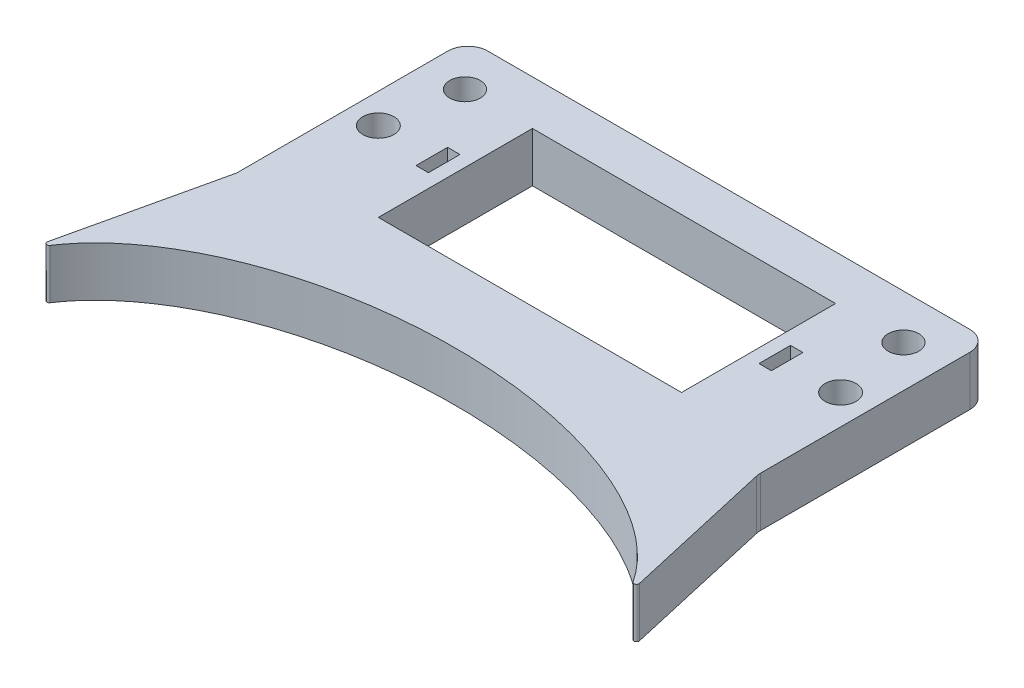
SolidWorks part; units mm, degrees
ref_plane "Front Plane" through (0, 0, 0) normal (0, 0, 1) x (1, 0, 0)
ref_plane "Top Plane" through (0, 0, 0) normal (0, 1, 0) x (1, 0, 0)
ref_plane "Right Plane" through (0, 0, 0) normal (1, 0, 0) x (0, 0, -1)
sketch "Sketch1" plane through (0, 0, 0) normal (0, 1, 0) x (1, 0, 0)
  line L1 (-52.5, -27.5) -> (52.5, -27.5)
  line L2 (-52.5, -27.5) -> (-52.5, 27.5)
  line L3 (-52.5, 27.5) -> (52.5, 27.5)
  line L4 (52.5, -27.5) -> (52.5, 27.5)
  line L5 (0, 27.5) -> (0, -27.5) construction
  line L6 (-52.5, 0) -> (52.5, 0) construction
  point P0 (0, 0)
  dimension "D1" = 105
  dimension "D2" = 55
extrude "Boss-Extrude1" add sketch "Sketch1" along normal blind 10
sketch "Sketch2" plane through (0, 10, 0) normal (0, 1, 0) x (1, 0, 0)
  line L6 (-30.5, 18.5) -> (30.5, 18.5)
  line L7 (-30.5, 18.5) -> (-30.5, -12.5)
  line L8 (-30.5, -12.5) -> (30.5, -12.5)
  line L9 (30.5, 18.5) -> (30.5, -12.5)
  line L10 (0, -12.5) -> (0, 18.5) construction
  line L11 (-30.5, 3) -> (30.5, 3) construction
  line L12 (0, 0) -> (0, -12.5) construction
  line L14 (-52.5, -27.5) -> (52.5, -27.5) construction
  point P0 (0, 3)
  dimension "D1" = 31
  dimension "D2" = 61
  dimension "D3" = 15
extrude "Cut-Extrude1" cut sketch "Sketch2" against normal through all
sketch "Sketch4" plane through (0, 10, 0) normal (0, 1, 0) x (1, 0, 0)
  line L2 (-46.5, 3.5) -> (-34.5, 3.5) construction
  line L3 (30.5, 18.5) -> (-30.5, 18.5) construction
  line L4 (-33.25, 6.675) -> (-35.75, 6.675)
  line L5 (-33.25, 6.675) -> (-33.25, 0.325)
  line L6 (-33.25, 0.325) -> (-35.75, 0.325)
  line L7 (-35.75, 6.675) -> (-35.75, 0.325)
  line L8 (-34.5, 0.325) -> (-34.5, 6.675) construction
  line L9 (-33.25, 3.5) -> (-35.75, 3.5) construction
  line L10 (-30.5, 18.5) -> (-30.5, -12.5) construction
  circle A0 centre (-46.5, 3.5) radius 3.125
  dimension "D1" = 6.25
  dimension "D2" = 15
  dimension "D3" = 16
  dimension "D4" = 2.5
  dimension "D5" = 6.35
  dimension "D6" = 2.75
extrude "Cut-Extrude3" cut sketch "Sketch4" against normal through all
sketch "Sketch5" plane through (0, 0, 0) normal (0, 1, 0) x (1, 0, 0)
  line L0 (0, 0) -> (0, -62.5) construction
  line L1 (-52.5, -27.5) -> (52.5, -27.5) construction
  line L2 (-52.5, -19.0391) -> (-60.2822, -53.2591)
  line L3 (-52.5, 27.5) -> (-52.5, -27.5) construction
  line L4 (-52.5, -19.0391) -> (0, -27.5)
  ellipse E0 centre (0, -62.5) end of major axis (-62.5, -62.5) minor radius 35
  point P14 (-60.0581, -51.0042)
  dimension "D1" = 125
  dimension "D2" = 62.5
extrude "Boss-Extrude2" add sketch "Sketch5" along normal up to surface (10 mm away) contours E0 L4 L2 region at (-40.4501, 0, 30.082) up to face at (-46.5, 10, -0.375)
sketch "Sketch6" plane through (0, 10, 0) normal (0, 1, 0) x (1, 0, 0)
  circle A0 centre (-44.1085, 18.5417) radius 3.075
  point P2 (-44.1085, 18.5417)
  dimension "D1" = 6.15
extrude "Cut-Extrude4" cut sketch "Sketch6" against normal through all
mirror "Mirror1" about plane through (0, 0, 0) normal (1, 0, 0) of "Cut-Extrude4", "Boss-Extrude2", "Cut-Extrude3"
fillet "Fillet1" radius 4 4 edges at (-52.5, 5, 19.0391) (52.5, 5, 19.0391) (52.5, 5, -27.5) (-52.5, 5, -27.5)
fillet "Fillet2" radius 0.5 2 edges at (60.2822, 5, 53.2591) (-60.2822, 5, 53.2591)
